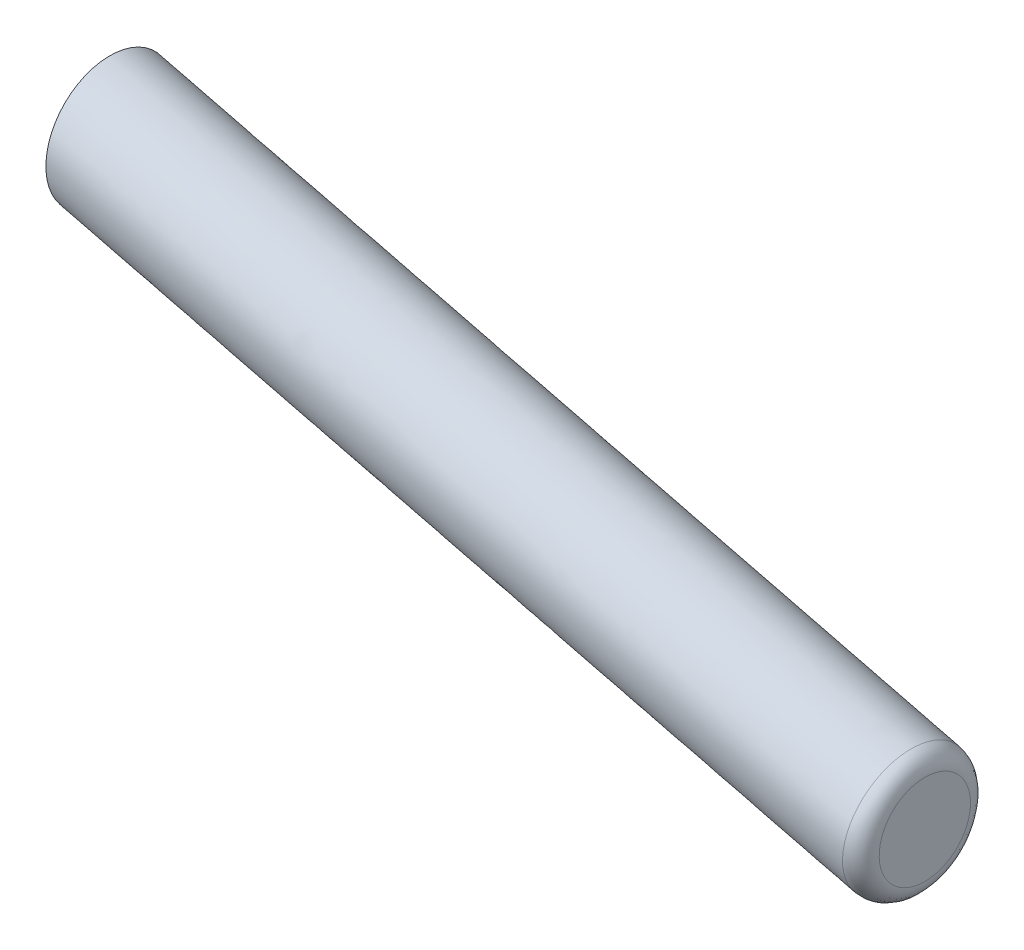
SolidWorks part; units mm, degrees
ref_plane "Front Plane" through (0, 0, 0) normal (0, 0, 1) x (1, 0, 0)
ref_plane "Top Plane" through (0, 0, 0) normal (0, 1, 0) x (1, 0, 0)
ref_plane "Right Plane" through (0, 0, 0) normal (1, 0, 0) x (0, 0, -1)
sketch "Sketch1" plane through (0, 0, 0) normal (1, 0, 0) x (0, 0, -1)
  circle A0 centre (0, 0) radius 17.5
  dimension "D1" = 35
sketch "Sketch3" plane through (0, 0, 0) normal (0, 0, 1) x (1, 0, 0)
  line L3 (0, 0) -> (223.1708, -55.6309)
  dimension "D3" = 230
sweep "Sweep2" add profiles "Sketch1" path "Sketch3"
fillet "Fillet1" radius 5 1 edges at (223.1708, -55.6309, -17.5) type face fillet first side face at (223.1708, -55.6309, -17.5) second side face at (223.1708, -55.6309, -17.5)
